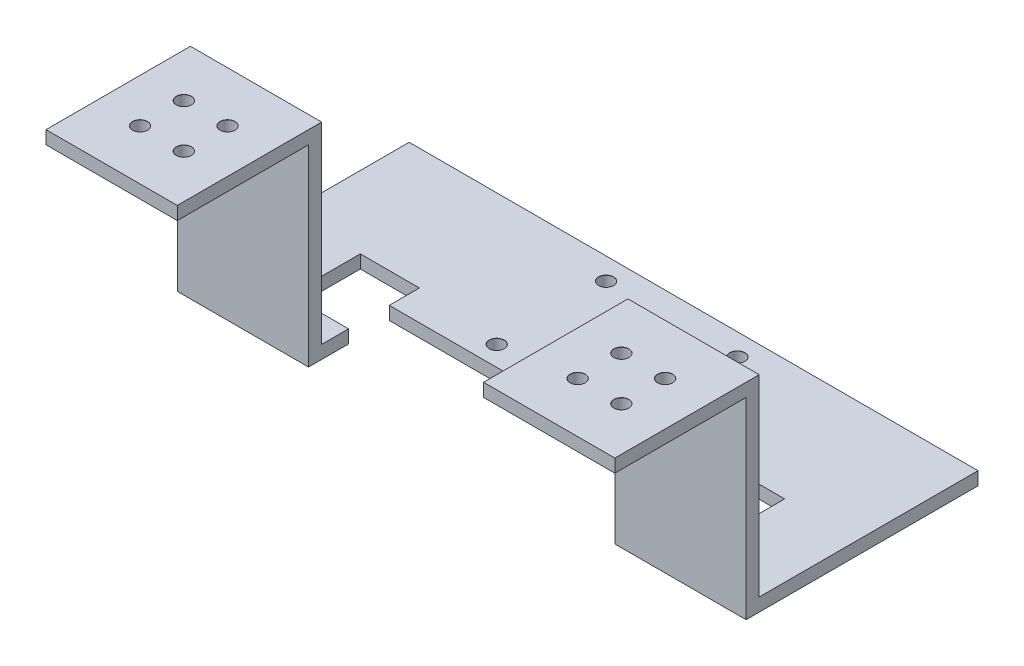
SolidWorks part; units mm, degrees
ref_plane "Front Plane" through (0, 0, 0) normal (0, 0, 1) x (1, 0, 0)
ref_plane "Top Plane" through (0, 0, 0) normal (0, 1, 0) x (1, 0, 0)
ref_plane "Right Plane" through (0, 0, 0) normal (1, 0, 0) x (0, 0, -1)
sketch "Sketch1" plane through (0, 0, 0) normal (1, 0, 0) x (0, 0, -1)
  line L0 (0, 44) -> (30, 44)
  line L1 (30, 44) -> (30, 0)
  line L2 (33, 3) -> (83, 3)
  line L3 (0, 44) -> (0, 47)
  line L4 (0, 47) -> (33, 47)
  line L5 (33, 47) -> (33, 3)
  line L6 (30, 0) -> (83, 0)
  line L7 (83, 0) -> (83, 3)
  dimension "D1" = 44
  dimension "D2" = 30
  dimension "D3" = 50
  dimension "D4" = 3
  dimension "D5" = 3
  dimension "D6" = 3
extrude "Boss-Extrude1" add sketch "Sketch1" along normal blind 130
sketch "Sketch2" plane through (0, 47, 0) normal (0, 1, 0) x (1, 0, 0)
  line L0 (130, 0) -> (0, 0) construction
  line L1 (30, 0) -> (100, 0)
  line L2 (30, 0) -> (30, 43)
  line L3 (30, 43) -> (100, 43)
  line L12 (100, 0) -> (100, 43)
  line L13 (130, 0) -> (0, 0) construction
  line L14 (65, 0) -> (65, 83) construction
  line L15 (130, 83) -> (0, 83) construction
  line L16 (130, 33) -> (0, 33) construction
  line L17 (130, 33) -> (0, 33) construction
  line M6 (0, 0) -> (130, 0)
  line M8 (130, 33) -> (0, 33)
  dimension "D2" = 10
  dimension "D1" = 70
extrude "Cut-Extrude1" cut sketch "Sketch2" against normal blind 130 contours L12 L2 M6 M8 | L12 L3 L2 M8 region at (65, 47, -16.5) region at (65, 47, -38)
hole_wizard "M3 Clearance Hole1" positions "Sketch3" profile "Sketch4" hole size "M3" standard "ANSI Metric" end condition through all
sketch "Sketch3" plane through (0, 47, 0) normal (0, 1, 0) x (1, 0, 0)
  line L0 (65, 83) -> (65, 0) construction
  line L1 (130, 83) -> (0, 83) construction
  line L3 (0, 16.5) -> (130, 16.5) construction
  line L4 (0, 33) -> (0, 0) construction
  line L5 (130, 33) -> (130, 0) construction
  line L6 (10, 21.5) -> (10, 11.5) construction
  line L7 (10, 11.5) -> (20, 11.5) construction
  line L8 (20, 11.5) -> (20, 21.5) construction
  line L9 (20, 21.5) -> (10, 21.5) construction
  line L11 (15, 33) -> (15, 0) construction
  line L12 (30, 33) -> (0, 33) construction
  line L13 (30, 0) -> (0, 0) construction
  point P17 (10, 21.5)
  point P19 (20, 21.5)
  point P21 (10, 11.5)
  point P23 (20, 11.5)
  point P37 (20, 16.5)
  point P46 (15, 11.5)
  point P47 (120, 21.5)
  point P48 (110, 21.5)
  point P49 (110, 11.5)
  point P50 (120, 11.5)
  dimension "D1" = 10
sketch "Sketch4" plane through (120, 47, -11.5) normal (1, 0, 0) x (0, 0, 1)
  line L0 (0, 0) -> (0, 47)
  line L1 (0, 47) -> (1.7, 47)
  line L2 (1.7, 47) -> (1.7, 0.025)
  line L3 (1.7, 0.025) -> (1.725, 0)
  line L5 (1.725, 0) -> (0, 0)
  line L6 (-1.7, 0.025) -> (-1.725, 0) construction
  line L11 (0, -6.35) -> (0, 107.95) construction
  dimension "Thru Hole Dia." = 3.4
  dimension "Thru Hole Depth" = 47
  dimension "Near C'Sink Dia." = 3.45
  dimension "Near C'Sink Angle" = 90
hole_wizard "M3 Clearance Hole2" positions "Sketch5" profile "Sketch6" hole size "M3" standard "ANSI Metric" end condition through all
sketch "Sketch5" plane through (0, 3, 0) normal (0, 1, 0) x (1, 0, 0)
  line L0 (65, 83) -> (65, 43) construction
  line L1 (130, 83) -> (0, 83) construction
  line L2 (100, 43) -> (30, 43) construction
  line L3 (50, 78) -> (80, 78) construction
  line L4 (80, 78) -> (80, 53) construction
  line L5 (80, 53) -> (50, 53) construction
  line L6 (50, 53) -> (50, 78) construction
  point P9 (50, 78)
  point P11 (80, 78)
  point P13 (50, 53)
  point P15 (80, 53)
  point P25 (65, 78)
  dimension "D1" = 30
  dimension "D2" = 25
  dimension "D3" = 5
sketch "Sketch6" plane through (80, 3, -53) normal (1, 0, 0) x (0, 0, 1)
  line L0 (0, 0) -> (0, 3)
  line L1 (0, 3) -> (1.7, 3)
  line L2 (1.7, 3) -> (1.7, 0.025)
  line L3 (1.7, 0.025) -> (1.725, 0)
  line L5 (1.725, 0) -> (0, 0)
  line L6 (-1.7, 0.025) -> (-1.725, 0) construction
  line L11 (0, -6.35) -> (0, 107.95) construction
  dimension "Thru Hole Dia." = 3.4
  dimension "Thru Hole Depth" = 3
  dimension "Near C'Sink Dia." = 3.45
  dimension "Near C'Sink Angle" = 90
sketch "Sketch7" plane through (0, 3, 0) normal (0, 1, 0) x (1, 0, 0)
  line L0 (100, 43) -> (100, 33) construction
  line L1 (30, 43) -> (100, 43)
  line L2 (30, 43) -> (30, 48.45)
  line L3 (30, 48.45) -> (100, 48.45)
  line L4 (100, 43) -> (100, 48.45)
  circle A1 centre (50, 53) radius 1.725 construction
  dimension "D1" = 4.55
extrude "Cut-Extrude2" cut sketch "Sketch7" against normal blind 10
sketch "Sketch8" plane through (0, 3, 0) normal (0, 1, 0) x (1, 0, 0)
  line L0 (100, 48.45) -> (100, 33) construction
  line L1 (113.4956, 39.1508) -> (100, 39.1508)
  line L2 (113.4956, 39.1508) -> (113.4956, 55.3269)
  line L3 (113.4956, 55.3269) -> (100, 55.3269)
  line L4 (100, 39.1508) -> (100, 55.3269)
  line L5 (65, 83) -> (65, 48.45) construction
  line L6 (130, 83) -> (0, 83) construction
  line L7 (100, 48.45) -> (30, 48.45) construction
  line L8 (16.5044, 55.3269) -> (30, 55.3269)
  line L9 (30, 39.1508) -> (30, 55.3269)
  line L10 (16.5044, 39.1508) -> (30, 39.1508)
  line L11 (16.5044, 39.1508) -> (16.5044, 55.3269)
extrude "Cut-Extrude3" cut sketch "Sketch8" against normal through all
